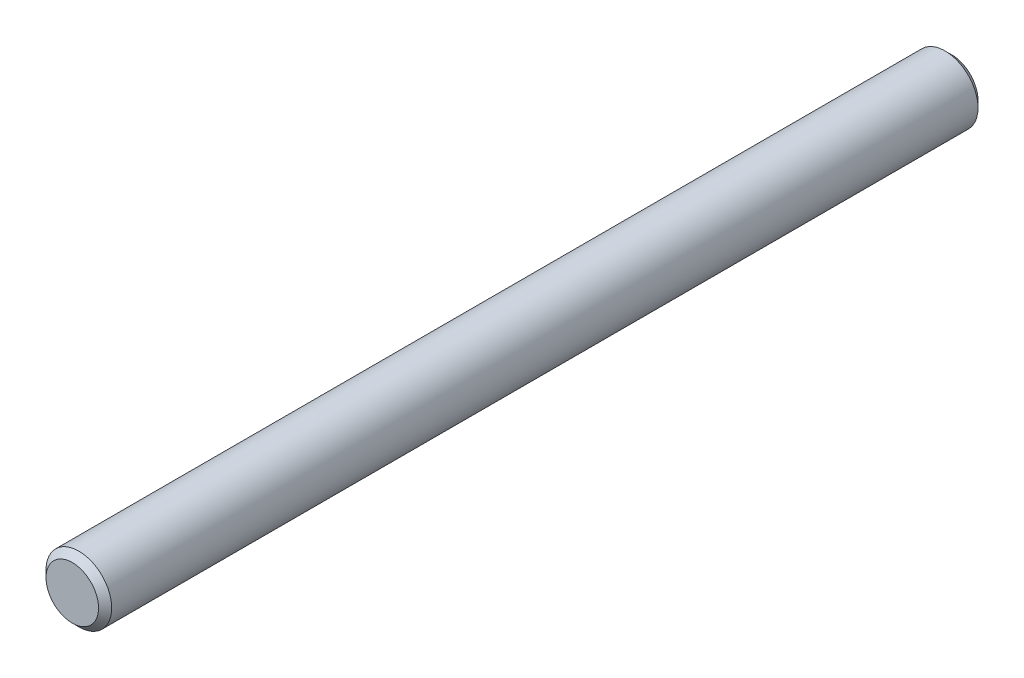
SolidWorks part; units mm, degrees
ref_plane "Front" through (0, 0, 0) normal (0, 0, 1) x (1, 0, 0)
ref_plane "Top" through (0, 0, 0) normal (0, 1, 0) x (1, 0, 0)
ref_plane "Right" through (0, 0, 0) normal (1, 0, 0) x (0, 0, -1)
sketch "Sketch1" plane through (0, 0, 0) normal (0, 0, 1) x (1, 0, 0)
  circle A0 centre (0, 0) radius 6.35
  dimension "dia" = 12.7
extrude "Extrude1" add sketch "Sketch1" along normal mid plane 170
sketch "Sketch2" plane through (0, 0, 0) normal (1, 0, 0) x (0, 0, -1)
  line L0 (85, 6.35) -> (70, 6.35) construction
  line L1 (85, 6.35) -> (-85, 6.35) construction
  line L2 (70, 6.35) -> (70, -6.35) construction
  line L3 (-85, -6.35) -> (85, -6.35) construction
  point P0 (-85, 6.35)
  point P1 (85, 6.35)
  dimension "D1" = 15
chamfer "Chamfer1" distance 1.27 angle 45 2 edges at (6.35, 0, -85) (6.35, 0, 85)
equation "\"D1@Chamfer1\" = \"dia@Sketch1\" * .1"
